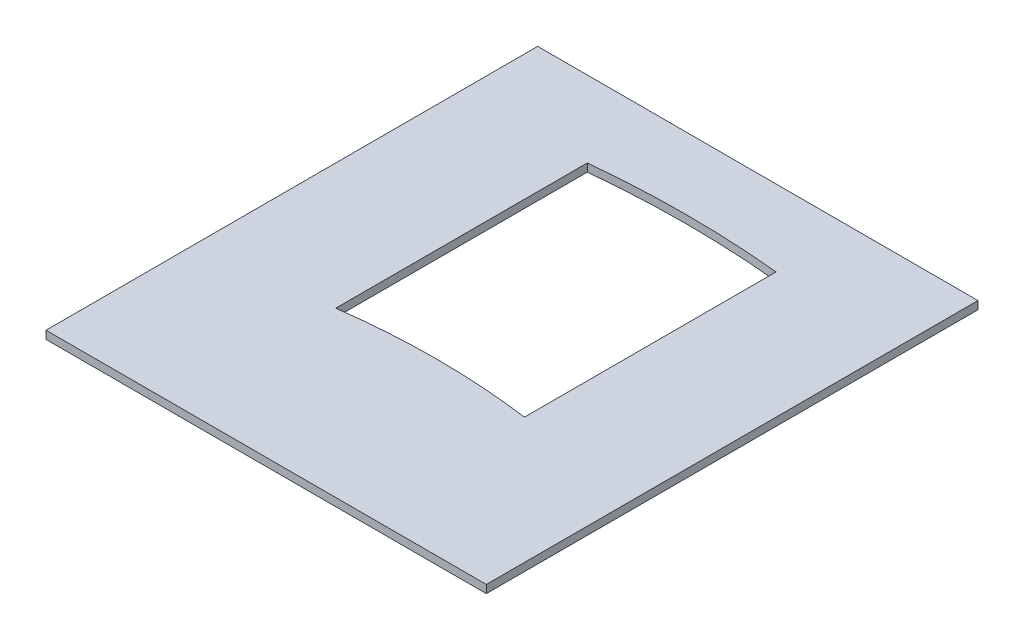
SolidWorks part; units mm, degrees
material "Copper"
ref_plane "Front" through (0, 0, 0) normal (0, 0, 1) x (1, 0, 0)
ref_plane "Top" through (0, 0, 0) normal (0, 1, 0) x (1, 0, 0)
ref_plane "Right" through (0, 0, 0) normal (1, 0, 0) x (0, 0, -1)
sketch "Sketch1" plane through (0, 0, 0) normal (0, 1, 0) x (1, 0, 0)
  line L0 (0, 0) -> (0, 4) construction
  line L2 (-1.6, 4) -> (-1.6, 0)
  line L3 (1.4, 4) -> (1.4, 0)
  line L4 (-3.6, 5.711) -> (-3.6, -2.6057)
  line L5 (3.4, 5.711) -> (3.4, -2.6057)
  line L6 (-3.6, 5.711) -> (3.4, 5.711)
  line L7 (-3.6, -2.6057) -> (3.4, -2.6057)
  line L8 (-3.6, 5.211) -> (3.4, 5.211)
  arc A1 (-1.6, 0) -> (1.4, 0) centre (-0.1, -10.8972) cw
  arc A2 (-1.6, 4) -> (1.4, 4) centre (-0.1, -10.9248) cw
  arc A5 (-3.6, -2.6057) -> (3.4, -2.6057) centre (-0.1, -10.8972) cw construction
  arc A7 (-3.6, 5.711) -> (3.4, 5.711) centre (-0.1, -10.9248) cw construction
  point P6 (0, 4)
  dimension "D1" = 4
  dimension "D2" = 11
  dimension "D4" = 15
  dimension "D6" = 0.5
  dimension "D3" = 3
  dimension "D5" = 2
extrude "Boss-Extrude1" add sketch "Sketch1" along normal blind 0.127 contours L8 L4 L7 L5 L2 A2 L3 A1 region at (-0.1, 0, -5.1061)
